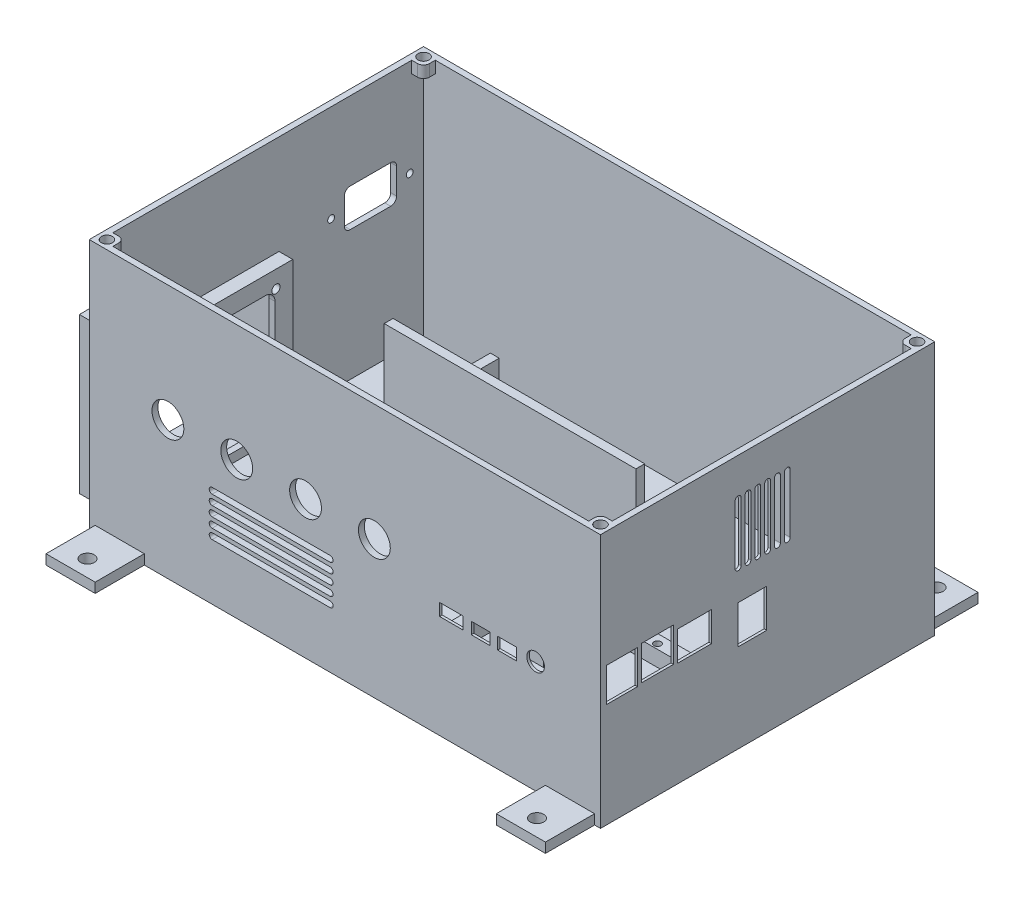
SolidWorks part; units mm, degrees
ref_plane "Front Plane" through (0, 0, 0) normal (0, 0, 1) x (1, 0, 0)
ref_plane "Top Plane" through (0, 0, 0) normal (0, 1, 0) x (1, 0, 0)
ref_plane "Right Plane" through (0, 0, 0) normal (1, 0, 0) x (0, 0, -1)
sketch "Sketch1" plane through (0, 0, 0) normal (0, 1, 0) x (1, 0, 0)
  line L1 (-130, -85) -> (130, -85)
  line L2 (-130, -85) -> (-130, 85)
  line L3 (-130, 85) -> (130, 85)
  line L4 (130, -85) -> (130, 85)
  line L5 (-130, -85) -> (130, 85) construction
  line L6 (-130, 85) -> (130, -85) construction
  point P0 (0, 0)
  dimension "D1" = 170
  dimension "D2" = 260
extrude "Floor" add sketch "Sketch1" along normal blind 4.3805
sketch "Sketch2" plane through (0, 4.3805, 0) normal (0, 1, 0) x (1, 0, 0)
  line L0 (127, -82) -> (127, 82)
  line L1 (127, 82) -> (-127, 82)
  line L2 (-127, 82) -> (-127, -82)
  line L3 (-127, -82) -> (127, -82)
  line L4 (130, -85) -> (130, 85)
  line L5 (130, 85) -> (-130, 85)
  line L6 (-130, 85) -> (-130, -85)
  line L7 (-130, -85) -> (130, -85)
  line L8 (130, -85) -> (130, 85)
  line L9 (130, 85) -> (-130, 85)
  line L10 (-130, 85) -> (-130, -85)
  line L11 (-130, -85) -> (130, -85)
  dimension "D1" = 0
  dimension "D2" = 3
extrude "Wall" add sketch "Sketch2" along normal blind 125
sketch "Sketch4" plane through (0, 4.3805, 0) normal (0, 1, 0) x (1, 0, 0)
  line L0 (120, -33) -> (49, -33)
  line L1 (127, -82) -> (42, -82)
  line L2 (127, -82) -> (127, -26)
  line L3 (127, -26) -> (42, -26)
  line L4 (42, -82) -> (42, -26)
  line L5 (49, -75) -> (49, -33)
  line L6 (120, -75) -> (49, -75)
  line L7 (120, -75) -> (120, -33)
  dimension "D1" = 85
  dimension "D2" = 56
  dimension "D3" = 7
extrude "Rpi stand" add sketch "Sketch4" along normal blind 8 from offset 29
sketch "Sketch7" plane through (0, 129.3805, 0) normal (0, 1, 0) x (1, 0, 0)
sketch "Sketch3" plane through (0, 0, 0) normal (0, 1, 0) x (1, 0, 0)
  line L0 (-114.3, 101.6) -> (114.3, 101.6) construction
  line L1 (-127, 85) -> (-102, 85)
  line L2 (-127, 85) -> (-127, 110)
  line L3 (-127, 110) -> (-102, 110)
  line L4 (-102, 85) -> (-102, 110)
  line L5 (127, 85) -> (102, 85)
  line L6 (127, 85) -> (127, 110)
  line L7 (127, 110) -> (102, 110)
  line L8 (102, 85) -> (102, 110)
  line L9 (-127, -85) -> (-102, -85)
  line L10 (-127, -85) -> (-127, -110)
  line L11 (-127, -110) -> (-102, -110)
  line L12 (-102, -85) -> (-102, -110)
  line L13 (127, -85) -> (102, -85)
  line L14 (127, -85) -> (127, -110)
  line L15 (127, -110) -> (102, -110)
  line L16 (102, -85) -> (102, -110)
  line L17 (114.3, 101.6) -> (114.3, -101.6) construction
  line L18 (114.3, -101.6) -> (-114.3, -101.6) construction
  line L19 (-114.3, -101.6) -> (-114.3, 101.6) construction
  line L20 (-130, 0) -> (130, 0) construction
  line L21 (130, 85) -> (-130, 85) construction
  line L22 (130, -85) -> (130, 85) construction
  line L23 (0, 101.6) -> (0, -101.6) construction
  line L24 (-130, -85) -> (130, -85) construction
  line L26 (-130, 85) -> (-130, -85) construction
  line L27 (-130, -85) -> (130, -85) construction
  circle A0 centre (-114.3, 101.6) radius 3.429
  circle A1 centre (114.3, 101.6) radius 3.429
  circle A2 centre (114.3, -101.6) radius 3.429
  circle A3 centre (-114.3, -101.6) radius 3.429
  point P4 (-130, -85)
  point P9 (130, -85)
  point P28 (-114.5, -85)
  point P29 (-102, -97.5)
  point P30 (114.5, -85)
  point P31 (-102, 97.5)
  dimension "D5" = 6.858
  dimension "D1" = 25
  dimension "D2" = 25
  dimension "D3" = 25
  dimension "D6" = 203.2
  dimension "D7" = 228.6
  dimension "D8" = 3
  dimension "D9" = 3
  dimension "D4" = 25
extrude "Brackets" add sketch "Sketch3" along normal blind 5
sketch "Sketch5" plane through (-130, 0, 0) normal (-1, 0, 0) x (0, 0, 1)
  line L0 (-8.5, 78.8805) -> (70, 78.8805)
  line L1 (-1, 4.3805) -> (62.5, 4.3805)
  line L2 (-4.5, 7.8805) -> (-4.5, 71.3805)
  line L3 (-1, 74.8805) -> (62.5, 74.8805)
  line L4 (66, 7.8805) -> (66, 71.3805)
  line L5 (70, 0.3805) -> (70, 78.8805)
  line L6 (-8.5, 0.3805) -> (70, 0.3805)
  line L7 (-8.5, 0.3805) -> (-8.5, 78.8805)
  line L8 (-4.5, 4.3805) -> (66, 4.3805) construction
  line L9 (110, 5) -> (110, 0) construction
  line L10 (-4.5, 4.3805) -> (-4.5, 74.8805) construction
  line L11 (-82, 4.3805) -> (82, 4.3805) construction
  line L12 (66, 4.3805) -> (66, 74.8805) construction
  line L13 (-4.5, 74.8805) -> (66, 74.8805) construction
  arc A0 (-1, 4.3805) -> (-4.5, 7.8805) centre (-1, 7.8805) cw
  arc A1 (62.5, 4.3805) -> (66, 7.8805) centre (62.5, 7.8805) ccw
  arc A2 (62.5, 74.8805) -> (66, 71.3805) centre (62.5, 71.3805) cw
  arc A3 (-4.5, 71.3805) -> (-1, 74.8805) centre (-1, 71.3805) cw
  dimension "D4" = 3.5
  dimension "D1" = 70.5
  dimension "D2" = 70.5
  dimension "D5" = 40
  dimension "D3" = 4
extrude "Fan Holder" add sketch "Sketch5" along normal blind 20 and the other way blind 10
sketch "Sketch31" plane through (0, 0.3805, 0) normal (0, -1, 0) x (1, 0, 0)
  line L4 (-130, -8.5) -> (-130, 70)
  line L5 (-130, 70) -> (-150, 70)
  line L6 (-150, 70) -> (-150, -8.5)
  line L7 (-150, -8.5) -> (-130, -8.5)
  line L8 (-130, -8.5) -> (-130, 70)
  line L9 (-130, 70) -> (-150, 70)
  line L10 (-150, 70) -> (-150, -8.5)
  line L11 (-150, -8.5) -> (-130, -8.5)
  dimension "D1" = 0
extrude "Bring fan holder to ground" add sketch "Sketch31" along normal up to surface (0.3805 mm away) up to face at (0, 0, 0)
sketch "Sketch8" plane through (-130, 0, 0) normal (-1, 0, 0) x (0, 0, 1)
  line L4 (-4.5, 71.3805) -> (-4.5, 7.8805)
  line L5 (-1, 4.3805) -> (62.5, 4.3805)
  line L6 (66, 7.8805) -> (66, 71.3805)
  line L7 (62.5, 74.8805) -> (-1, 74.8805)
  line L8 (-4.5, 71.3805) -> (-4.5, 7.8805)
  line L9 (-1, 4.3805) -> (62.5, 4.3805)
  line L10 (66, 7.8805) -> (66, 71.3805)
  line L23 (62.5, 74.8805) -> (-1, 74.8805)
  arc A2 (-4.5, 7.8805) -> (-1, 4.3805) centre (-1, 7.8805) ccw
  arc A3 (-4.5, 7.8805) -> (-1, 4.3805) centre (-1, 7.8805) ccw
  arc A4 (62.5, 4.3805) -> (66, 7.8805) centre (62.5, 7.8805) ccw
  arc A5 (62.5, 4.3805) -> (66, 7.8805) centre (62.5, 7.8805) ccw
  arc A8 (66, 71.3805) -> (62.5, 74.8805) centre (62.5, 71.3805) ccw
  arc A14 (66, 71.3805) -> (62.5, 74.8805) centre (62.5, 71.3805) ccw
  arc A16 (-1, 74.8805) -> (-4.5, 71.3805) centre (-1, 71.3805) ccw
  arc A17 (-1, 74.8805) -> (-4.5, 71.3805) centre (-1, 71.3805) ccw
  dimension "D1" = 0
extrude "Fan hole" cut sketch "Sketch8" against normal up to next
sketch "Sketch11" plane through (-120, 0, 0) normal (-1, 0, 0) x (0, 0, 1)
  line L0 (-8.5, 39.4402) -> (70, 39.4402) construction
  line L1 (30.75, 78.8805) -> (30.75, 0.3805) construction
  line L3 (0.05, 8.7402) -> (61.45, 8.7402) construction
  line L4 (-8.5, 78.8805) -> (-8.5, 0)
  line L5 (-8.5, 0) -> (70, 0)
  line L6 (70, 0) -> (70, 78.8805)
  line L7 (70, 78.8805) -> (-8.5, 78.8805)
  line L8 (-8.5, 78.8805) -> (-8.5, 0)
  line L10 (70, 0) -> (70, 78.8805)
  line L11 (70, 78.8805) -> (-8.5, 78.8805)
  line L12 (0.05, 8.7402) -> (0.05, 70.1402) construction
  line L13 (0.05, 70.1402) -> (61.45, 70.1402) construction
  line L14 (61.45, 8.7402) -> (61.45, 70.1402) construction
  line L15 (0.05, 8.7402) -> (61.45, 70.1402) construction
  line L16 (0.5, 69.8805) -> (0.5, 9)
  line L17 (0.5, 9) -> (61, 9)
  line L18 (61, 9) -> (61, 69.8805)
  line L19 (61, 69.8805) -> (0.5, 69.8805)
  line L20 (0.5, 64.8805) -> (0.5, 14)
  line L22 (61, 14) -> (61, 64.8805)
  line L23 (56, 69.8805) -> (5.5, 69.8805)
  line L24 (0.05, 70.1402) -> (61.45, 8.7402) construction
  line L29 (5.5, 9) -> (56, 9)
  line L31 (-8.5, 0) -> (70, 0)
  arc A0 (0.5, 14) -> (5.5, 9) centre (5.5, 14) ccw
  arc A1 (56, 9) -> (61, 14) centre (56, 14) ccw
  arc A2 (61, 64.8805) -> (56, 69.8805) centre (56, 64.8805) ccw
  arc A3 (0.5, 64.8805) -> (5.5, 69.8805) centre (5.5, 64.8805) cw
  circle A4 centre (0.05, 70.1402) radius 2.1
  circle A5 centre (61.45, 70.1402) radius 2.1
  circle A6 centre (61.45, 8.7402) radius 2.1
  circle A7 centre (0.05, 8.7402) radius 2.1
  point P24 (30.75, 39.4402)
  point P34 (30.75, 39.4402)
  dimension "D3" = 5
  dimension "D6" = 4.2
  dimension "D4" = 61.4
  dimension "D5" = 61.4
  dimension "D1" = 0
  dimension "D2" = 9
extrude "Boss-Extrude9" add sketch "Sketch11" along normal blind 3
sketch "Sketch12" plane through (0, 33.3805, 0) normal (0, -1, 0) x (1, 0, 0)
  line L1 (42, 26) -> (49, 26)
  line L2 (42, 26) -> (42, 33)
  line L3 (42, 33) -> (49, 33)
  line L4 (49, 26) -> (49, 33)
  dimension "D1" = 7
  dimension "D2" = 7
extrude "Boss-Extrude10" add sketch "Sketch12" along normal up to next
sketch "Sketch13" plane through (0, 4.3805, 0) normal (0, 1, 0) x (1, 0, 0)
  line L0 (127, 82) -> (-127, 82) construction
  line L2 (-107, -57) -> (-107, 5.7) construction
  line L3 (-107, 5.7) -> (-69.4, 5.7) construction
  line L4 (-107, -57) -> (-69.4, -57) construction
  line L5 (-69.4, 5.7) -> (-69.4, -57) construction
  line L6 (-69.4, 5.7) -> (-57.4, 5.7) construction
  line L7 (-57.4, 5.7) -> (-57.4, -57) construction
  line L8 (-57.4, -57) -> (-19.8, -57) construction
  line L9 (-19.8, -57) -> (-19.8, 5.7) construction
  line L10 (-19.8, 5.7) -> (-57.4, 5.7) construction
  line L11 (-69.4, -57) -> (-57.4, -57) construction
  line L12 (-19.8, -57) -> (62.83, -57) construction
  line L13 (62.83, -57) -> (62.83, -25.4) construction
  line L14 (62.83, -25.4) -> (105, -25.4) construction
  line L15 (105, -25.4) -> (105, -57) construction
  line L16 (105, -57) -> (62.83, -57) construction
  line L17 (118, 82) -> (118, 21.5) construction
  line L18 (-16.3, -57.85) -> (-16.3, 6.55) construction
  line L20 (127, -82) -> (127, 82) construction
  line L21 (118, 21.5) -> (120.7, 21.5) construction
  line L22 (118, 21.5) -> (41.5, 21.5) construction
  line L23 (-6.3, -47) -> (30.69, -47) construction
  line L24 (-6.3, -47) -> (-6.3, -6.4) construction
  line L25 (-6.3, -6.4) -> (30.69, -6.4) construction
  line L26 (30.69, -47) -> (30.69, -6.4) construction
  line L27 (-6.3, -47) -> (30.69, -6.4) construction
  line L28 (-6.3, -6.4) -> (30.69, -47) construction
  line L29 (130, -85) -> (130, 85) construction
  line L30 (-127, -82) -> (127, -82) construction
  line L457 (-127, 8.5) -> (-127, -70) construction
  line L458 (-127, -82) -> (127, -82) construction
  circle A0 centre (-107, -57) radius 1.25
  circle A1 centre (-107, 5.7) radius 1.25
  circle A2 centre (-69.4, 5.7) radius 1.25
  circle A3 centre (-69.4, -57) radius 1.25
  circle A4 centre (-57.4, 5.7) radius 1.25
  circle A5 centre (-57.4, -57) radius 1.25
  circle A6 centre (-19.8, -57) radius 1.25
  circle A7 centre (-19.8, 5.7) radius 1.25
  circle A12 centre (120.7, 21.5) radius 1.25
  circle A13 centre (41.5, 21.5) radius 1.25
  circle A14 centre (-107, 5.7) radius 2.75
  circle A15 centre (-107, -57) radius 2.75
  circle A16 centre (-69.4, 5.7) radius 2.75
  circle A17 centre (-57.4, 5.7) radius 2.75
  circle A18 centre (-69.4, -57) radius 2.75
  circle A19 centre (-57.4, -57) radius 2.75
  circle A20 centre (-19.8, -57) radius 2.75
  circle A21 centre (-19.8, 5.7) radius 2.75
  circle A22 centre (62.83, -57) radius 2.5
  circle A23 centre (62.83, -25.4) radius 2.5
  circle A24 centre (105, -25.4) radius 2.5
  circle A25 centre (105, -57) radius 2.5
  circle A26 centre (-6.3, -47) radius 1.25
  circle A28 centre (-6.3, -47) radius 2.75
  circle A30 centre (-69.4, 5.7) radius 1.65 construction
  circle A31 centre (104.2333, -41.2) radius 1.5 construction
  circle A32 centre (104.2333, -41.2) radius 1.5 construction
  circle A33 centre (63.5933, -41.2) radius 1.5 construction
  circle A34 centre (63.5933, -41.2) radius 1.5 construction
  circle A35 centre (104.2333, -41.2) radius 3
  circle A36 centre (63.5933, -41.2) radius 3
  circle A37 centre (-6.3, -6.4) radius 1.25
  circle A38 centre (30.69, -6.4) radius 1.25
  circle A39 centre (30.69, -47) radius 1.25
  circle A40 centre (-6.3, -6.4) radius 2.75
  circle A41 centre (30.69, -6.4) radius 2.75
  circle A42 centre (30.69, -47) radius 2.75
  circle A43 centre (30.69, -6.4) radius 1.5 construction
  circle A44 centre (30.69, -6.4) radius 1.5 construction
  point P2 (-127, -82)
  point P3 (127, -82)
  point P8 (12.195, -26.7)
  point P31 (127, 82)
  point P32 (-127, 82)
  point P90 (-123, -62.5)
  point P91 (-123, -66)
  point P92 (-130, -70)
  point P93 (-130, 8.5)
  point P94 (-127, 8.5)
  point P95 (-127, -70)
  point P96 (-127, 8.5)
  point P97 (-120, 8.5)
  point P98 (-120, -70)
  point P99 (-127, -70)
  point P100 (-120, 8.5)
  point P101 (-120, -70)
  point P102 (-130, -85)
  point P103 (-127, -85)
  point P104 (-102, -85)
  point P105 (102, -85)
  point P106 (127, -85)
  point P107 (130, -85)
  point P108 (-130, 85)
  point P109 (-130, -85)
  point P110 (130, 85)
  point P111 (127, 85)
  point P112 (102, 85)
  point P113 (-102, 85)
  point P114 (-127, 85)
  point P115 (-130, 85)
  point P116 (130, -85)
  point P117 (130, 85)
  point P118 (-130, 85)
  point P119 (-130, -85)
  point P120 (130, 85)
  point P121 (-130, 85)
  point P122 (130, -85)
  point P123 (130, 85)
  point P124 (-130, -85)
  point P125 (130, -85)
  point P126 (-127, 82)
  point P127 (-127, -82)
  point P128 (127, 82)
  point P129 (-127, 82)
  point P130 (127, -82)
  point P131 (127, 82)
  point P132 (-127, -82)
  point P133 (127, -82)
  point P134 (-127, 82)
  point P135 (-127, 8.5)
  point P136 (-127, -70)
  point P137 (-127, -82)
  point P138 (127, -82)
  point P139 (127, 82)
  point P140 (42, -82)
  point P141 (127, -82)
  point P142 (42, -26)
  point P143 (42, -82)
  point P144 (127, -26)
  point P145 (42, -26)
  point P146 (127, -82)
  point P147 (127, -26)
  point P148 (42, -82)
  point P149 (127, -82)
  point P150 (42, -33)
  point P151 (42, -82)
  point P152 (127, -26)
  point P153 (49, -26)
  point P154 (127, -82)
  point P155 (127, -26)
  point P156 (49, -75)
  point P157 (120, -75)
  point P158 (49, -33)
  point P159 (49, -75)
  point P160 (120, -33)
  point P161 (49, -33)
  point P162 (120, -75)
  point P163 (120, -33)
  point P164 (49, -75)
  point P165 (120, -75)
  point P166 (49, -33)
  point P167 (49, -75)
  point P168 (120, -33)
  point P169 (49, -33)
  point P170 (120, -75)
  point P171 (120, -33)
  point P172 (-102, 110)
  point P173 (-127, 110)
  point P174 (-102, 85)
  point P175 (-102, 110)
  point P176 (-127, 85)
  point P177 (-102, 85)
  point P178 (-127, 110)
  point P179 (-127, 85)
  point P180 (-102, 110)
  point P181 (-127, 110)
  point P182 (-102, 85)
  point P183 (-102, 110)
  point P184 (-127, 110)
  point P185 (-127, 85)
  point P186 (-114.3, 101.6)
  point P187 (-111.0208, 102.6025)
  point P188 (-114.3, 101.6)
  point P189 (-111.0208, 102.6025)
  point P190 (114.3, 101.6)
  point P191 (117.5792, 102.6025)
  point P192 (114.3, 101.6)
  point P193 (117.5792, 102.6025)
  point P194 (127, 85)
  point P195 (127, 110)
  point P196 (127, 110)
  point P197 (102, 110)
  point P198 (102, 110)
  point P199 (102, 85)
  point P200 (127, 85)
  point P201 (127, 110)
  point P202 (127, 110)
  point P203 (102, 110)
  point P204 (102, 110)
  point P205 (102, 85)
  point P206 (102, 85)
  point P207 (127, 85)
  point P208 (-114.3, -101.6)
  point P209 (-111.0208, -100.5975)
  point P210 (-114.3, -101.6)
  point P211 (-111.0208, -100.5975)
  point P212 (-127, -85)
  point P213 (-127, -110)
  point P214 (-127, -110)
  point P215 (-102, -110)
  point P216 (-102, -110)
  point P217 (-102, -85)
  point P218 (-127, -85)
  point P219 (-127, -110)
  point P220 (-127, -110)
  point P221 (-102, -110)
  point P222 (-102, -110)
  point P223 (-102, -85)
  point P224 (-102, -85)
  point P225 (-127, -85)
  point P226 (114.3, -101.6)
  point P227 (117.5792, -100.5975)
  point P228 (114.3, -101.6)
  point P229 (117.5792, -100.5975)
  point P230 (127, -110)
  point P231 (127, -85)
  point P232 (102, -85)
  point P233 (102, -110)
  point P234 (102, -110)
  point P235 (127, -110)
  point P236 (127, -110)
  point P237 (127, -85)
  point P238 (127, -85)
  point P239 (102, -85)
  point P240 (102, -85)
  point P241 (102, -110)
  point P242 (102, -110)
  point P243 (127, -110)
  point P244 (-130, 8.5)
  point P245 (-130, -70)
  point P246 (-120, 8.5)
  point P247 (-127, 8.5)
  point P248 (-130, 8.5)
  point P249 (-150, 8.5)
  point P250 (-120, -70)
  point P251 (-127, -70)
  point P252 (-130, -70)
  point P253 (-150, -70)
  point P254 (-130, -70)
  point P255 (-150, -70)
  point P256 (-130, 8.5)
  point P257 (-150, 8.5)
  point P258 (-120, -70)
  point P259 (-120, 8.5)
  point P260 (-123, 4.5)
  point P261 (-150, 4.5)
  point P262 (-123, 4.5)
  point P263 (-150, 4.5)
  point P264 (-123, 1)
  point P265 (-150, 1)
  point P266 (-123, -62.5)
  point P267 (-150, -62.5)
  point P268 (-123, -66)
  point P269 (-150, -66)
  point P270 (-123, -66)
  point P271 (-150, -66)
  point P272 (-123, -62.5)
  point P273 (-150, -62.5)
  point P274 (-123, 1)
  point P275 (-150, 1)
  point P276 (-150, -70)
  point P277 (-150, 8.5)
  point P278 (-150, 8.5)
  point P279 (-150, -70)
  point P280 (-150, 4.5)
  point P281 (-150, 1)
  point P282 (-150, -62.5)
  point P283 (-150, 1)
  point P284 (-150, -62.5)
  point P285 (-150, -66)
  point P286 (-150, -62.5)
  point P287 (-150, -66)
  point P288 (-150, 1)
  point P289 (-150, -62.5)
  point P290 (-150, 4.5)
  point P291 (-150, 1)
  point P292 (-123, 4.5)
  point P293 (-123, 1)
  point P294 (-123, -62.5)
  point P295 (-123, 1)
  point P296 (-123, 4.5)
  point P297 (-123, 1)
  point P298 (-123, 1)
  point P299 (-123, -62.5)
  point P300 (-123, -62.5)
  point P301 (-123, -66)
  point P302 (-123, -5.5)
  point P303 (-120, -5.5)
  point P304 (-123, -56)
  point P305 (-120, -56)
  point P306 (-123, -61)
  point P307 (-120, -61)
  point P308 (-123, -61)
  point P309 (-120, -61)
  point P310 (-123, -56)
  point P311 (-120, -56)
  point P312 (-123, -5.5)
  point P313 (-120, -5.5)
  point P314 (-123, -0.5)
  point P315 (-120, -0.5)
  point P316 (-123, -0.5)
  point P317 (-120, -0.5)
  point P318 (-123, -0.5)
  point P319 (-123, -5.5)
  point P320 (-123, -56)
  point P321 (-123, -5.5)
  point P322 (-123, -56)
  point P323 (-123, -61)
  point P324 (-123, -56)
  point P325 (-123, -61)
  point P326 (-123, -5.5)
  point P327 (-123, -56)
  point P328 (-123, -0.5)
  point P329 (-123, -5.5)
  point P330 (-120, -5.5)
  point P331 (-120, -0.5)
  point P332 (-120, -56)
  point P333 (-120, -5.5)
  point P334 (-120, -61)
  point P335 (-120, -56)
  point P336 (-120, -61)
  point P337 (-120, -56)
  point P338 (-120, -5.5)
  point P339 (-120, -56)
  point P340 (-120, -5.5)
  point P341 (-120, -0.5)
  point P342 (-123, 2.05)
  point P343 (-123, -2.15)
  point P344 (-120, -2.15)
  point P345 (-120, 2.05)
  point P346 (-123, -59.35)
  point P347 (-123, -63.55)
  point P348 (-120, -63.55)
  point P349 (-120, -59.35)
  point P350 (-123, -59.35)
  point P351 (-123, -63.55)
  point P352 (-120, -63.55)
  point P353 (-120, -59.35)
  point P354 (-123, 2.05)
  point P355 (-123, -2.15)
  point P356 (-120, -2.15)
  point P357 (-120, 2.05)
  point P358 (49, -33)
  point P359 (42, -33)
  point P360 (49, -26)
  point P361 (49, -33)
  point P362 (42, -33)
  point P363 (42, -26)
  point P364 (42, -26)
  point P365 (49, -26)
  point P366 (49, -26)
  point P367 (49, -33)
  point P368 (49, -33)
  point P369 (42, -33)
  point P370 (-130, -85)
  point P371 (130, -85)
  point P372 (-130, -85)
  point P373 (-130, 85)
  point P374 (-130, 85)
  point P375 (130, 85)
  point P376 (130, -85)
  point P377 (130, 85)
  point P378 (-130, -85)
  point P379 (130, 85)
  point P380 (-130, 85)
  point P381 (130, -85)
  point P382 (127, -82)
  point P383 (127, 82)
  point P384 (127, 82)
  point P385 (-127, 82)
  point P386 (-127, 82)
  point P387 (-127, -82)
  point P388 (-127, -82)
  point P389 (127, -82)
  point P390 (130, -85)
  point P391 (130, 85)
  point P392 (130, 85)
  point P393 (-130, 85)
  point P394 (-130, 85)
  point P395 (-130, -85)
  point P396 (-130, -85)
  point P397 (130, -85)
  point P398 (130, -85)
  point P399 (130, 85)
  point P400 (130, 85)
  point P401 (-130, 85)
  point P402 (-130, 85)
  point P403 (-130, -85)
  point P404 (-130, -85)
  point P405 (130, -85)
  point P406 (120, -33)
  point P407 (49, -33)
  point P408 (127, -82)
  point P409 (42, -82)
  point P410 (127, -82)
  point P411 (127, -26)
  point P412 (127, -26)
  point P413 (42, -26)
  point P414 (42, -82)
  point P415 (42, -26)
  point P416 (49, -75)
  point P417 (49, -33)
  point P418 (120, -75)
  point P419 (49, -75)
  point P420 (120, -75)
  point P421 (120, -33)
  point P422 (-114.3, 101.6)
  point P423 (114.3, 101.6)
  point P424 (-127, 85)
  point P425 (-102, 85)
  point P426 (-127, 85)
  point P427 (-127, 110)
  point P428 (-127, 110)
  point P429 (-102, 110)
  point P430 (-102, 85)
  point P431 (-102, 110)
  point P432 (127, 85)
  point P433 (102, 85)
  point P434 (127, 85)
  point P435 (127, 110)
  point P436 (127, 110)
  point P437 (102, 110)
  point P438 (102, 85)
  point P439 (102, 110)
  point P440 (-127, -85)
  point P441 (-102, -85)
  point P442 (-127, -85)
  point P443 (-127, -110)
  point P444 (-127, -110)
  point P445 (-102, -110)
  point P446 (-102, -85)
  point P447 (-102, -110)
  point P448 (127, -85)
  point P449 (102, -85)
  point P450 (127, -85)
  point P451 (127, -110)
  point P452 (127, -110)
  point P453 (102, -110)
  point P454 (102, -85)
  point P455 (102, -110)
  point P456 (114.3, 101.6)
  point P457 (114.3, -101.6)
  point P458 (114.3, -101.6)
  point P459 (-114.3, -101.6)
  point P460 (-114.3, -101.6)
  point P461 (-114.3, 101.6)
  point P462 (-130, 0)
  point P463 (130, 0)
  point P464 (130, 85)
  point P465 (-130, 85)
  point P466 (130, -85)
  point P467 (130, 85)
  point P468 (0, 101.6)
  point P469 (0, -101.6)
  point P470 (-130, 85)
  point P471 (-130, -85)
  point P472 (-130, -85)
  point P473 (130, -85)
  point P474 (-130, 8.5)
  point P475 (-130, -70)
  point P476 (-130, 1)
  point P477 (-130, -62.5)
  point P478 (-130, 1)
  point P479 (-130, -62.5)
  point P480 (-130, 8.5)
  point P481 (-130, -70)
  point P482 (-130, 4.5)
  point P483 (-130, -66)
  point P484 (-130, 82)
  point P485 (-130, -82)
  point P486 (-130, 4.5)
  point P487 (-130, -66)
  point P488 (-130, 1)
  point P489 (-130, -62.5)
  point P490 (-130, -62.5)
  point P491 (-130, 1)
  point P492 (-130, 1)
  point P493 (-130, -62.5)
  point P494 (-130, -62.5)
  point P495 (-130, 1)
  point P496 (-120, 8.5)
  point P497 (-120, -70)
  point P498 (-120, -0.05)
  point P499 (-120, -61.45)
  point P500 (-120, 8.5)
  point P501 (-120, -70)
  point P502 (-120, -70)
  point P503 (-120, 8.5)
  point P504 (-120, 8.5)
  point P505 (-120, -70)
  point P506 (-120, -70)
  point P507 (-120, 8.5)
  point P508 (-120, -0.05)
  point P509 (-120, -61.45)
  point P510 (-120, -0.05)
  point P511 (-120, -61.45)
  point P512 (-120, -0.5)
  point P513 (-120, -61)
  point P514 (-120, -61)
  point P515 (-120, -0.5)
  point P516 (-120, -5.5)
  point P517 (-120, -56)
  point P518 (-120, -56)
  point P519 (-120, -5.5)
  point P520 (-120, -0.05)
  point P521 (-120, -61.45)
  point P522 (42, -26)
  point P523 (49, -26)
  point P524 (42, -26)
  point P525 (42, -33)
  point P526 (42, -33)
  point P527 (49, -33)
  point P528 (49, -26)
  point P529 (49, -33)
  point P530 (-123, -62.5)
  point P531 (-123, -66)
  point P532 (-130, -70)
  point P533 (-130, 8.5)
  point P534 (-127, 8.5)
  point P535 (-127, -70)
  point P536 (-127, 8.5)
  point P537 (-120, 8.5)
  point P538 (-120, -70)
  point P539 (-127, -70)
  point P540 (-120, 8.5)
  point P541 (-120, -70)
  point P542 (-130, -85)
  point P543 (-127, -85)
  point P544 (-102, -85)
  point P545 (102, -85)
  point P546 (127, -85)
  point P547 (130, -85)
  point P548 (-130, 85)
  point P549 (-130, -85)
  point P550 (130, 85)
  point P551 (127, 85)
  point P552 (102, 85)
  point P553 (-102, 85)
  point P554 (-127, 85)
  point P555 (-130, 85)
  point P556 (130, -85)
  point P557 (130, 85)
  point P558 (-130, 85)
  point P559 (-130, -85)
  point P560 (130, 85)
  point P561 (-130, 85)
  point P562 (130, -85)
  point P563 (130, 85)
  point P564 (-130, -85)
  point P565 (130, -85)
  point P566 (-127, 82)
  point P567 (-127, -82)
  point P568 (127, 82)
  point P569 (-127, 82)
  point P570 (127, -82)
  point P571 (127, 82)
  point P572 (-127, -82)
  point P573 (127, -82)
  point P574 (-127, 82)
  point P575 (-127, 8.5)
  point P576 (-127, -70)
  point P577 (-127, -82)
  point P578 (127, 82)
  point P579 (-127, 82)
  point P580 (127, -82)
  point P581 (127, 82)
  point P582 (-127, -82)
  point P583 (127, -82)
  point P584 (42, -82)
  point P585 (127, -82)
  point P586 (42, -26)
  point P587 (42, -82)
  point P588 (127, -26)
  point P589 (42, -26)
  point P590 (127, -82)
  point P591 (127, -26)
  point P592 (42, -82)
  point P593 (127, -82)
  point P594 (42, -33)
  point P595 (42, -82)
  point P596 (127, -26)
  point P597 (49, -26)
  point P598 (127, -82)
  point P599 (127, -26)
  point P600 (49, -75)
  point P601 (120, -75)
  point P602 (49, -33)
  point P603 (49, -75)
  point P604 (120, -33)
  point P605 (49, -33)
  point P606 (120, -75)
  point P607 (120, -33)
  point P608 (49, -75)
  point P609 (120, -75)
  point P610 (49, -33)
  point P611 (49, -75)
  point P612 (120, -33)
  point P613 (49, -33)
  point P614 (120, -75)
  point P615 (120, -33)
  point P616 (-102, 110)
  point P617 (-127, 110)
  point P618 (-102, 85)
  point P619 (-102, 110)
  point P620 (-127, 85)
  point P621 (-102, 85)
  point P622 (-127, 110)
  point P623 (-127, 85)
  point P624 (-102, 110)
  point P625 (-127, 110)
  point P626 (-102, 85)
  point P627 (-102, 110)
  point P628 (-127, 110)
  point P629 (-127, 85)
  point P630 (-114.3, 101.6)
  point P631 (-111.0208, 102.6025)
  point P632 (-114.3, 101.6)
  point P633 (-111.0208, 102.6025)
  point P634 (114.3, 101.6)
  point P635 (117.5792, 102.6025)
  point P636 (114.3, 101.6)
  point P637 (117.5792, 102.6025)
  point P638 (127, 85)
  point P639 (127, 110)
  point P640 (127, 110)
  point P641 (102, 110)
  point P642 (102, 110)
  point P643 (102, 85)
  point P644 (127, 85)
  point P645 (127, 110)
  point P646 (127, 110)
  point P647 (102, 110)
  point P648 (102, 110)
  point P649 (102, 85)
  point P650 (102, 85)
  point P651 (127, 85)
  point P652 (-114.3, -101.6)
  point P653 (-111.0208, -100.5975)
  point P654 (-114.3, -101.6)
  point P655 (-111.0208, -100.5975)
  point P656 (-127, -85)
  point P657 (-127, -110)
  point P658 (-127, -110)
  point P659 (-102, -110)
  point P660 (-102, -110)
  point P661 (-102, -85)
  point P662 (-127, -85)
  point P663 (-127, -110)
  point P664 (-127, -110)
  point P665 (-102, -110)
  point P666 (-102, -110)
  point P667 (-102, -85)
  point P668 (-102, -85)
  point P669 (-127, -85)
  point P670 (114.3, -101.6)
  point P671 (117.5792, -100.5975)
  point P672 (114.3, -101.6)
  point P673 (117.5792, -100.5975)
  point P674 (127, -110)
  point P675 (127, -85)
  point P676 (102, -85)
  point P677 (102, -110)
  point P678 (102, -110)
  point P679 (127, -110)
  point P680 (127, -110)
  point P681 (127, -85)
  point P682 (127, -85)
  point P683 (102, -85)
  point P684 (102, -85)
  point P685 (102, -110)
  point P686 (102, -110)
  point P687 (127, -110)
  point P688 (-130, 8.5)
  point P689 (-130, -70)
  point P690 (-120, 8.5)
  point P691 (-127, 8.5)
  point P692 (-130, 8.5)
  point P693 (-150, 8.5)
  point P694 (-120, -70)
  point P695 (-127, -70)
  point P696 (-130, -70)
  point P697 (-150, -70)
  point P698 (-130, -70)
  point P699 (-150, -70)
  point P700 (-130, 8.5)
  point P701 (-150, 8.5)
  point P702 (-120, -70)
  point P703 (-120, 8.5)
  point P704 (-123, 4.5)
  point P705 (-150, 4.5)
  point P706 (-123, 4.5)
  point P707 (-150, 4.5)
  point P708 (-123, 1)
  point P709 (-150, 1)
  point P710 (-123, -62.5)
  point P711 (-150, -62.5)
  point P712 (-123, -66)
  point P713 (-150, -66)
  point P714 (-123, -66)
  point P715 (-150, -66)
  point P716 (-123, -62.5)
  point P717 (-150, -62.5)
  point P718 (-123, 1)
  point P719 (-150, 1)
  point P720 (-150, -70)
  point P721 (-150, 8.5)
  point P722 (-150, 8.5)
  point P723 (-150, -70)
  point P724 (-150, 4.5)
  point P725 (-150, 1)
  point P726 (-150, -62.5)
  point P727 (-150, 1)
  point P728 (-150, -62.5)
  point P729 (-150, -66)
  point P730 (-150, -62.5)
  point P731 (-150, -66)
  point P732 (-150, 1)
  point P733 (-150, -62.5)
  point P734 (-150, 4.5)
  point P735 (-150, 1)
  point P736 (-123, 4.5)
  point P737 (-123, 1)
  point P738 (-123, -62.5)
  point P739 (-123, 1)
  point P740 (-123, 4.5)
  point P741 (-123, 1)
  point P742 (-123, 1)
  point P743 (-123, -62.5)
  point P744 (-123, -62.5)
  point P745 (-123, -66)
  point P746 (-123, -5.5)
  point P747 (-120, -5.5)
  point P748 (-123, -56)
  point P749 (-120, -56)
  point P750 (-123, -61)
  point P751 (-120, -61)
  point P752 (-123, -61)
  point P753 (-120, -61)
  point P754 (-123, -56)
  point P755 (-120, -56)
  point P756 (-123, -5.5)
  point P757 (-120, -5.5)
  point P758 (-123, -0.5)
  point P759 (-120, -0.5)
  point P760 (-123, -0.5)
  point P761 (-120, -0.5)
  point P762 (-123, -0.5)
  point P763 (-123, -5.5)
  point P764 (-123, -56)
  point P765 (-123, -5.5)
  point P766 (-123, -56)
  point P767 (-123, -61)
  point P768 (-123, -56)
  point P769 (-123, -61)
  point P770 (-123, -5.5)
  point P771 (-123, -56)
  point P772 (-123, -0.5)
  point P773 (-123, -5.5)
  point P774 (-120, -5.5)
  point P775 (-120, -0.5)
  point P776 (-120, -56)
  point P777 (-120, -5.5)
  point P778 (-120, -61)
  point P779 (-120, -56)
  point P780 (-120, -61)
  point P781 (-120, -56)
  point P782 (-120, -5.5)
  point P783 (-120, -56)
  point P784 (-120, -5.5)
  point P785 (-120, -0.5)
  point P786 (-123, 2.05)
  point P787 (-123, -2.15)
  point P788 (-120, -2.15)
  point P789 (-120, 2.05)
  point P790 (-123, -59.35)
  point P791 (-123, -63.55)
  point P792 (-120, -63.55)
  point P793 (-120, -59.35)
  point P794 (-123, -59.35)
  point P795 (-123, -63.55)
  point P796 (-120, -63.55)
  point P797 (-120, -59.35)
  point P798 (-123, 2.05)
  point P799 (-123, -2.15)
  point P800 (-120, -2.15)
  point P801 (-120, 2.05)
  point P802 (49, -33)
  point P803 (42, -33)
  point P804 (49, -26)
  point P805 (49, -33)
  point P806 (42, -33)
  point P807 (42, -26)
  point P808 (42, -26)
  point P809 (49, -26)
  point P810 (49, -26)
  point P811 (49, -33)
  point P812 (49, -33)
  point P813 (42, -33)
  point P814 (-130, -85)
  point P815 (130, -85)
  point P816 (-130, -85)
  point P817 (-130, 85)
  point P818 (-130, 85)
  point P819 (130, 85)
  point P820 (130, -85)
  point P821 (130, 85)
  point P822 (-130, -85)
  point P823 (130, 85)
  point P824 (-130, 85)
  point P825 (130, -85)
  point P826 (127, -82)
  point P827 (127, 82)
  point P828 (127, 82)
  point P829 (-127, 82)
  point P830 (-127, 82)
  point P831 (-127, -82)
  point P832 (-127, -82)
  point P833 (127, -82)
  point P834 (130, -85)
  point P835 (130, 85)
  point P836 (130, 85)
  point P837 (-130, 85)
  point P838 (-130, 85)
  point P839 (-130, -85)
  point P840 (-130, -85)
  point P841 (130, -85)
  point P842 (130, -85)
  point P843 (130, 85)
  point P844 (130, 85)
  point P845 (-130, 85)
  point P846 (-130, 85)
  point P847 (-130, -85)
  point P848 (-130, -85)
  point P849 (130, -85)
  point P850 (120, -33)
  point P851 (49, -33)
  point P852 (127, -82)
  point P853 (42, -82)
  point P854 (127, -82)
  point P855 (127, -26)
  point P856 (127, -26)
  point P857 (42, -26)
  point P858 (42, -82)
  point P859 (42, -26)
  point P860 (49, -75)
  point P861 (49, -33)
  point P862 (120, -75)
  point P863 (49, -75)
  point P864 (120, -75)
  point P865 (120, -33)
  point P866 (-114.3, 101.6)
  point P867 (114.3, 101.6)
  point P868 (-127, 85)
  point P869 (-102, 85)
  point P870 (-127, 85)
  point P871 (-127, 110)
  point P872 (-127, 110)
  point P873 (-102, 110)
  point P874 (-102, 85)
  point P875 (-102, 110)
  point P876 (127, 85)
  point P877 (102, 85)
  point P878 (127, 85)
  point P879 (127, 110)
  point P880 (127, 110)
  point P881 (102, 110)
  point P882 (102, 85)
  point P883 (102, 110)
  point P884 (-127, -85)
  point P885 (-102, -85)
  point P886 (-127, -85)
  point P887 (-127, -110)
  point P888 (-127, -110)
  point P889 (-102, -110)
  point P890 (-102, -85)
  point P891 (-102, -110)
  point P892 (127, -85)
  point P893 (102, -85)
  point P894 (127, -85)
  point P895 (127, -110)
  point P896 (127, -110)
  point P897 (102, -110)
  point P898 (102, -85)
  point P899 (102, -110)
  point P900 (114.3, 101.6)
  point P901 (114.3, -101.6)
  point P902 (114.3, -101.6)
  point P903 (-114.3, -101.6)
  point P904 (-114.3, -101.6)
  point P905 (-114.3, 101.6)
  point P906 (-130, 0)
  point P907 (130, 0)
  point P908 (130, 85)
  point P909 (-130, 85)
  point P910 (130, -85)
  point P911 (130, 85)
  point P912 (0, 101.6)
  point P913 (0, -101.6)
  point P914 (-130, 85)
  point P915 (-130, -85)
  point P916 (-130, -85)
  point P917 (130, -85)
  point P918 (-130, 8.5)
  point P919 (-130, -70)
  point P920 (-130, 1)
  point P921 (-130, -62.5)
  point P922 (-130, 1)
  point P923 (-130, -62.5)
  point P924 (-130, 8.5)
  point P925 (-130, -70)
  point P926 (-130, 4.5)
  point P927 (-130, -66)
  point P928 (-130, 82)
  point P929 (-130, -82)
  point P930 (-130, 4.5)
  point P931 (-130, -66)
  point P932 (-130, 1)
  point P933 (-130, -62.5)
  point P934 (-130, -62.5)
  point P935 (-130, 1)
  point P936 (-130, 1)
  point P937 (-130, -62.5)
  point P938 (-130, -62.5)
  point P939 (-130, 1)
  point P940 (-120, 8.5)
  point P941 (-120, -70)
  point P942 (-120, -0.05)
  point P943 (-120, -61.45)
  point P944 (-120, 8.5)
  point P945 (-120, -70)
  point P946 (-120, -70)
  point P947 (-120, 8.5)
  point P948 (-120, 8.5)
  point P949 (-120, -70)
  point P950 (-120, -70)
  point P951 (-120, 8.5)
  point P952 (-120, -0.05)
  point P953 (-120, -61.45)
  point P954 (-120, -0.05)
  point P955 (-120, -61.45)
  point P956 (-120, -0.5)
  point P957 (-120, -61)
  point P958 (-120, -61)
  point P959 (-120, -0.5)
  point P960 (-120, -5.5)
  point P961 (-120, -56)
  point P962 (-120, -56)
  point P963 (-120, -5.5)
  point P964 (-120, -0.05)
  point P965 (-120, -61.45)
  point P966 (42, -26)
  point P967 (49, -26)
  point P968 (42, -26)
  point P969 (42, -33)
  point P970 (42, -33)
  point P971 (49, -33)
  point P972 (49, -26)
  point P973 (49, -33)
  dimension "D3" = 2.5
  dimension "D6" = 1.5
  dimension "D7" = 2.5
  dimension "D8" = 10
  dimension "D11" = 35
  dimension "D12" = 20
  dimension "D13" = 25
  dimension "D25" = 2.5
  dimension "D27" = 2.5
  dimension "D4" = 5
  dimension "D5" = 25
  dimension "D9" = 12
  dimension "D10" = 1.5
  dimension "D17" = 31.6
  dimension "D19" = 42.17
  dimension "D22" = 60.5
  dimension "D23" = 9
  dimension "D24" = 2.7
  dimension "D26" = 76.5
  dimension "D28" = 1.5
extrude "Built in Standoffs" add sketch "Sketch13" along normal blind 5 contours A1 | A16 A2 | A2 | A17 A4 | A4 | A14 A1 | A21 A7 | A7 | A15 A0 | A0 | A18 A3 | A3 | A19 A5 | A5 | A20 A6 | A6 | A22 | A23 | A24 A32 | A32 | A25 | A36 | A35 | A28 A26 | A26 | A40 A37 | A37 | A41 A38 | A38 | A42 A39 | A39 region at (-107, 4.3805, 57) region at (-107, 4.3805, -5.7) region at (-69.4, 4.3805, -5.7) region at (-69.4, 4.3805, 57) region at (-57.4, 4.3805, -5.7) region at (-57.4, 4.3805, 57) region at (-19.8, 4.3805, 57) region at (-19.8, 4.3805, -5.7) region at (-109.6722, 4.3805, -5.7) region at (-109.6722, 4.3805, 57) region at (-72.0722, 4.3805, -5.7) region at (-60.0722, 4.3805, -5.7) region at (-72.0722, 4.3805, 57) region at (-60.0722, 4.3805, 57) region at (-22.4722, 4.3805, 57) region at (-22.4722, 4.3805, -5.7) region at (62.83, 4.3805, 57) region at (62.83, 4.3805, 25.4) region at (105, 4.3805, 25.4) region at (105, 4.3805, 57) region at (-6.3, 4.3805, 47) region at (-8.9722, 4.3805, 47) region at (104.2333, 4.3805, 41.2) region at (63.5933, 4.3805, 41.2) region at (-6.3, 4.3805, 6.4) region at (30.69, 4.3805, 6.4) region at (30.69, 4.3805, 47) region at (-8.9722, 4.3805, 6.4) region at (28.0178, 4.3805, 6.4) region at (28.0178, 4.3805, 47)
sketch "Sketch19" plane through (0, 9.3805, 0) normal (0, 1, 0) x (1, 0, 0)
  circle A0 centre (104.2333, -41.2) radius 1.25
  circle A1 centre (63.5933, -41.2) radius 1.25
  dimension "D1" = 2.5
  dimension "D2" = 2.5
extrude "Bread board holes" cut sketch "Sketch19" against normal blind 7
sketch "Sketch14" plane through (0, 4.3805, 0) normal (0, 1, 0) x (1, 0, 0)
  line L0 (127, 82) -> (-88, 82)
  line L1 (127, 82) -> (-127, 82) construction
  line L2 (-88, 82) -> (-88, 32)
  line L3 (-88, 32) -> (127, 32)
  line L4 (127, -82) -> (127, 82) construction
  line L5 (127, 32) -> (127, 82)
  dimension "D1" = 215
  dimension "D2" = 50
extrude "Screw Holes" cut sketch "Sketch13<4>" against normal blind 7 from surface contours A37 | A38 | A26 | A39 | A1 | A0 | A3 | A5 | A2 | A4 | A7 | A6 | A32 region at (-6.3, 4.3805, 47) region at (-6.3, 4.3805, 6.4) region at (30.69, 4.3805, 6.4) region at (30.69, 4.3805, 47) starting at face at (-107, 9.3805, -2.95)
sketch "Sketch13<4>" plane through (0, 4.3805, 0) normal (0, 1, 0) x (1, 0, 0) same geometry as "Sketch13"
extrude "Driver Screw Holes" cut sketch "Sketch13<5>" against normal blind 3 contours A13 | A12
sketch "Sketch13<5>" plane through (0, 4.3805, 0) normal (0, 1, 0) x (1, 0, 0) same geometry as "Sketch13"
sketch "Sketch16" plane through (0, 4.3805, 0) normal (0, 1, 0) x (1, 0, 0)
  line L0 (-93, 82) -> (-93, 28)
  line L1 (-93, 28) -> (35, 28)
  line L2 (-88.5, 82) -> (-88.5, 32.5)
  line L3 (-88.5, 32.5) -> (35, 32.5)
  line L10 (-88, 82) -> (-88, 33) construction
  line L11 (-88, 33) -> (29.1074, 33) construction
  line L14 (-93, 28) -> (127, 28) construction
  line L16 (-88, 33) -> (127, 33) construction
  line L17 (-88.5, 82) -> (-93, 82)
  line L20 (35, 28) -> (35, 32.5)
  line L21 (-88.5, 32.5) -> (29.1074, 32.5) construction
  line L25 (-88, 33) -> (127, 33)
  line L26 (127, 33) -> (127, 82)
  line L27 (127, 82) -> (-88, 82)
  line L28 (-88, 82) -> (-88, 33)
  line L29 (-88, 33) -> (127, 33) construction
  line L30 (127, 33) -> (127, 82) construction
  line L31 (127, 82) -> (-88, 82) construction
  line L32 (-88, 82) -> (-88, 33) construction
  line L57 (-88, 82) -> (-88, 33) construction
  line L58 (127, 82) -> (-127, 82) construction
  dimension "D3" = 0.5
  dimension "D5" = 128
  dimension "D1" = 0
  dimension "D2" = 5
extrude "Power supply wall" add sketch "Sketch16" along normal blind 10 contours L2 L3 L20 L1 L0 L17
sketch "Sketch25" plane through (0, 14.3805, 0) normal (0, 1, 0) x (1, 0, 0)
  line L0 (-93, 82) -> (-93, 28) construction
  line L1 (35, 28) -> (-93, 28)
  line L2 (35, 28) -> (35, 32.5)
  line L3 (35, 32.5) -> (-93, 32.5)
  line L4 (-93, 28) -> (-93, 32.5)
  line L5 (-88.5, 32.5) -> (35, 32.5) construction
  line L6 (-88.5, 32.5) -> (35, 32.5) construction
extrude "Boss-Extrude11" add sketch "Sketch25" along normal blind 40
sketch "Sketch17" plane through (0, 41.3805, 0) normal (0, 1, 0) x (1, 0, 0)
  circle A0 centre (46.5, -30.5) radius 1.7859
  circle A1 centre (104.5, -30.5) radius 1.7859
  circle A2 centre (104.5, -79.5) radius 1.7859
  circle A3 centre (46.5, -79.5) radius 1.7859
  dimension "D1" = 3.5719
extrude "rpi standoff holes" cut sketch "Sketch17" against normal blind 6
sketch "Sketch20" plane through (0, 0, 85) normal (0, 0, 1) x (1, 0, 0)
  line L1 (49.6827, 57.1504) -> (58.6882, 57.1504) construction
  line L2 (49.6827, 57.1504) -> (49.6827, 53.9554) construction
  line L3 (49.6827, 53.9554) -> (58.6882, 53.9554) construction
  line L4 (58.6882, 57.1504) -> (58.6882, 53.9554) construction
  line L5 (79.2167, 56.9908) -> (85.8798, 56.9908) construction
  line L6 (79.2167, 56.9908) -> (79.2167, 53.9258) construction
  line L7 (79.2167, 53.9258) -> (85.8798, 53.9258) construction
  line L8 (85.8798, 56.9908) -> (85.8798, 53.9258) construction
  line L9 (65.7798, 56.9112) -> (72.2962, 56.9112) construction
  line L10 (65.7798, 56.9112) -> (65.7798, 53.9475) construction
  line L11 (65.7798, 53.9475) -> (72.2962, 53.9475) construction
  line L12 (72.2962, 56.9112) -> (72.2962, 53.9475) construction
  line L13 (48.1827, 58.6504) -> (60.1882, 58.6504)
  line L14 (60.1882, 58.6504) -> (60.1882, 52.4554)
  line L15 (48.1827, 52.4554) -> (60.1882, 52.4554)
  line L16 (48.1827, 58.6504) -> (48.1827, 52.4554)
  line L17 (77.7167, 58.4908) -> (87.3798, 58.4908)
  line L18 (87.3798, 58.4908) -> (87.3798, 52.4258)
  line L19 (77.7167, 52.4258) -> (87.3798, 52.4258)
  line L20 (77.7167, 58.4908) -> (77.7167, 52.4258)
  line L21 (64.2798, 58.4112) -> (73.7962, 58.4112)
  line L22 (73.7962, 58.4112) -> (73.7962, 52.4475)
  line L23 (64.2798, 52.4475) -> (73.7962, 52.4475)
  line L24 (64.2798, 58.4112) -> (64.2798, 52.4475)
  circle A0 centre (97, 56.9705) radius 4.5
  dimension "D1" = 9
  dimension "D2" = 1.5
extrude "Cut-Extrude5" cut sketch "Sketch20" against normal up to next
sketch "Sketch21" plane through (0, 129.3805, 0) normal (0, 1, 0) x (1, 0, 0)
  line L0 (125, -26.3) -> (46, -26.3) construction
  line L1 (42.3, -30) -> (42.3, -80) construction
  line L2 (46, -83.7) -> (125, -83.7)
  line L3 (128.7, -80) -> (128.7, -30)
  line L4 (128, -80) -> (128, -30)
  line L5 (125, -27) -> (46, -27)
  line L6 (43, -30) -> (43, -80)
  line L7 (46, -83) -> (125, -83)
  line L8 (128, -80) -> (128, -30) construction
  line L9 (125, -27) -> (46, -27) construction
  line L10 (43, -30) -> (43, -80) construction
  line L11 (46, -83) -> (125, -83) construction
  line L28 (46, -83.7) -> (20.659, -83.7)
  line L29 (20.659, -83.7) -> (20.659, 4.3626)
  line L30 (20.659, 4.3626) -> (128.7, 4.3626)
  line L31 (128.7, 4.3626) -> (128.7, -30)
  arc A0 (46, -26.3) -> (42.3, -30) centre (46, -30) ccw construction
  arc A1 (42.3, -80) -> (46, -83.7) centre (46, -80) ccw construction
  arc A2 (125, -83.7) -> (128.7, -80) centre (125, -80) ccw
  arc A3 (128.7, -30) -> (125, -26.3) centre (125, -30) ccw construction
  arc A4 (128, -30) -> (125, -27) centre (125, -30) ccw
  arc A5 (46, -27) -> (43, -30) centre (46, -30) ccw
  arc A6 (43, -80) -> (46, -83) centre (46, -80) ccw
  arc A7 (125, -83) -> (128, -80) centre (125, -80) ccw
  arc A8 (128, -30) -> (125, -27) centre (125, -30) ccw construction
  arc A9 (46, -27) -> (43, -30) centre (46, -30) ccw construction
  arc A10 (43, -80) -> (46, -83) centre (46, -80) ccw construction
  arc A11 (125, -83) -> (128, -80) centre (125, -80) ccw construction
  dimension "D1" = 0
  dimension "D2" = 0.7
extrude "Rpi Room" cut sketch "Sketch21" against normal up to surface (88 mm away) from offset 20 contours L2 A2 L3 L31 L30 L29 L28 up to face at (46.5, 41.3805, 81.2859) offset against normal yes
sketch "Sketch22" plane through (130, 0, 0) normal (1, 0, 0) x (0, 0, -1)
  line L0 (-81.966, 70.2905) -> (-66.1499, 70.2905)
  line L1 (-81.166, 69.4905) -> (-66.9499, 69.4905) construction
  line L2 (-81.166, 69.4905) -> (-81.166, 53.8427) construction
  line L3 (-81.166, 53.8427) -> (-66.9499, 53.8427) construction
  line L4 (-66.9499, 69.4905) -> (-66.9499, 53.8427) construction
  line L5 (-63.3011, 70.2905) -> (-48.6526, 70.2905) construction
  line L6 (-63.3011, 70.2905) -> (-63.3011, 54.5222) construction
  line L7 (-63.3011, 54.5222) -> (-48.6526, 54.5222) construction
  line L8 (-48.6526, 70.2905) -> (-48.6526, 54.5222) construction
  line L9 (-45.1414, 67.4119) -> (-29.3586, 67.4119) construction
  line L10 (-45.1414, 67.4119) -> (-45.1414, 53.9605) construction
  line L11 (-45.1414, 53.9605) -> (-29.3586, 53.9605) construction
  line L12 (-29.3586, 67.4119) -> (-29.3586, 53.9605) construction
  line L13 (-66.1499, 70.2905) -> (-66.1499, 53.0427)
  line L14 (-81.966, 53.0427) -> (-66.1499, 53.0427)
  line L15 (-81.966, 70.2905) -> (-81.966, 53.0427)
  line L16 (-64.1011, 71.0905) -> (-47.8526, 71.0905)
  line L17 (-47.8526, 71.0905) -> (-47.8526, 53.7222)
  line L18 (-64.1011, 53.7222) -> (-47.8526, 53.7222)
  line L19 (-64.1011, 71.0905) -> (-64.1011, 53.7222)
  line L20 (-45.9414, 68.2119) -> (-28.5586, 68.2119)
  line L21 (-28.5586, 68.2119) -> (-28.5586, 53.1605)
  line L22 (-45.9414, 53.1605) -> (-28.5586, 53.1605)
  line L23 (-45.9414, 68.2119) -> (-45.9414, 53.1605)
  line L24 (-70.9672, 69.4905) -> (-73.95, 69.4905) construction
  line L25 (-85, 129.3805) -> (-85, 0) construction
  line L26 (-85, 0) -> (85, 0) construction
  arc A0 (-29.3, 67.2705) -> (-29.5, 67.4705) centre (-29.5, 67.2705) ccw construction
  dimension "D2" = 3.834
  dimension "D3" = 14.2161
  dimension "D4" = 15.6478
  dimension "D5" = 3.6488
  dimension "D6" = 14.6485
  dimension "D7" = 15.7683
  dimension "D8" = 70.2905
  dimension "D9" = 13.4514
  dimension "D1" = 0.8
extrude "Cut-Extrude7" cut sketch "Sketch22" against normal up to next
sketch "Sketch24" plane through (0, 0, -85) normal (0, 0, -1) x (-1, 0, 0)
  circle A0 centre (-83.6, 40.8805) radius 30 construction
  circle A1 centre (-83.6, 40.8805) radius 30 construction
  circle A2 centre (-83.6, 40.8805) radius 32
  dimension "D1" = 2
extrude "Cut-Extrude8" cut sketch "Sketch24" against normal up to next
sketch "Sketch26" plane through (130, 0, 0) normal (1, 0, 0) x (0, 0, -1)
  line L0 (-15, 80) -> (-15, 110) construction
  line L1 (-16.5, 80) -> (-16.5, 110)
  line L2 (-13.5, 80) -> (-13.5, 110)
  line L3 (-85, 0) -> (85, 0) construction
  line L4 (-85, 129.3805) -> (-85, 0) construction
  line L5 (-10, 80) -> (-10, 110) construction
  line L6 (-11.5, 80) -> (-11.5, 110)
  line L7 (-8.5, 80) -> (-8.5, 110)
  line L8 (-5, 80) -> (-5, 110) construction
  line L9 (-6.5, 80) -> (-6.5, 110)
  line L10 (-3.5, 80) -> (-3.5, 110)
  line L11 (0, 80) -> (0, 110) construction
  line L12 (-1.5, 80) -> (-1.5, 110)
  line L13 (1.5, 80) -> (1.5, 110)
  line L14 (5, 80) -> (5, 110) construction
  line L15 (3.5, 80) -> (3.5, 110)
  line L16 (6.5, 80) -> (6.5, 110)
  line L17 (10, 80) -> (10, 110) construction
  line L18 (8.5, 80) -> (8.5, 110)
  line L19 (11.5, 80) -> (11.5, 110)
  arc A0 (-16.5, 80) -> (-13.5, 80) centre (-15, 80) ccw
  arc A1 (-13.5, 110) -> (-16.5, 110) centre (-15, 110) ccw
  arc A2 (-11.5, 80) -> (-8.5, 80) centre (-10, 80) ccw
  arc A3 (-8.5, 110) -> (-11.5, 110) centre (-10, 110) ccw
  arc A4 (-6.5, 80) -> (-3.5, 80) centre (-5, 80) ccw
  arc A5 (-3.5, 110) -> (-6.5, 110) centre (-5, 110) ccw
  arc A6 (-1.5, 80) -> (1.5, 80) centre (0, 80) ccw
  arc A7 (1.5, 110) -> (-1.5, 110) centre (0, 110) ccw
  arc A8 (3.5, 80) -> (6.5, 80) centre (5, 80) ccw
  arc A9 (6.5, 110) -> (3.5, 110) centre (5, 110) ccw
  arc A10 (8.5, 80) -> (11.5, 80) centre (10, 80) ccw
  arc A11 (11.5, 110) -> (8.5, 110) centre (10, 110) ccw
  point P2 (-15, 95)
  point P14 (-10, 95)
  point P21 (-5, 95)
  point P28 (0, 95)
  point P35 (5, 95)
  point P42 (10, 95)
  dimension "D1" = 30
  dimension "D2" = 3
  dimension "D3" = 80
  dimension "D4" = 70
  dimension "D6" = 5
  dimension "D5" = 6
extrude "vent 1" cut sketch "Sketch26" against normal up to next
sketch "Sketch27" plane through (0, 129.3805, 0) normal (0, 1, 0) x (1, 0, 0)
  line L0 (0, 0) -> (0, 85) construction
  line L1 (130, 85) -> (121, 85)
  line L2 (130, 85) -> (130, 76)
  line L3 (130, 76) -> (124, 76)
  line L4 (121, 85) -> (121, 79)
  line L18 (-130, 0) -> (130, 0) construction
  line L20 (-121, 85) -> (-121, 79)
  line L21 (-130, 76) -> (-124, 76)
  line L22 (-130, 85) -> (-130, 76)
  line L23 (-130, 85) -> (-121, 85)
  line L24 (-130, -85) -> (-121, -85)
  line L25 (-130, -85) -> (-130, -76)
  line L26 (-130, -76) -> (-124, -76)
  line L27 (-121, -85) -> (-121, -79)
  line L28 (121, -85) -> (121, -79)
  line L29 (130, -76) -> (124, -76)
  line L30 (130, -85) -> (130, -76)
  line L31 (130, -85) -> (121, -85)
  circle A0 centre (125.5, 80.5) radius 2.8067
  circle A1 centre (-125.5, 80.5) radius 2.8067
  circle A2 centre (-125.5, -80.5) radius 2.8067
  circle A3 centre (125.5, -80.5) radius 2.8067
  arc A4 (124, 76) -> (121, 79) centre (124, 79) cw
  arc A5 (121, -79) -> (124, -76) centre (124, -79) cw
  arc A6 (-124, -76) -> (-121, -79) centre (-124, -79) cw
  arc A7 (-121, 79) -> (-124, 76) centre (-124, 79) cw
  point P23 (121, 76)
  point P35 (121, -76)
  point P38 (-121, -76)
  point P41 (-121, 76)
  dimension "D1" = 5.6134
  dimension "D5" = 3
  dimension "D6" = 3
  dimension "D2" = 4.5
  dimension "D3" = 4.5
  dimension "D4" = 9
extrude "Boss-Extrude12" add sketch "Sketch27" against normal blind 6 contours L21 A7 L20 L23 L22 | L30 L29 A5 L28 L31 | L2 L3 A4 L4 L1 | L24 L27 A6 L26 L25
extrude "lid holes" cut sketch "Sketch27<3>" against normal blind 4.8 contours A0 | A1 | A2 | A3
sketch "Sketch27<3>" plane through (0, 129.3805, 0) normal (0, 1, 0) x (1, 0, 0) same geometry as "Sketch27"
sketch "Sketch28" plane through (0, 0, 85) normal (0, 0, 1) x (1, 0, 0)
  line L0 (-102, 0) -> (102, 0) construction
  line L1 (-130, 129.3805) -> (-130, 0) construction
  line L2 (-90, 70) -> (-55, 70) construction
  circle A0 centre (-90, 70) radius 8.1
  circle A4 centre (-55, 70) radius 8.1
  circle A5 centre (-20, 70) radius 8.1
  circle A6 centre (15, 70) radius 8.1
  dimension "D1" = 16.2
  dimension "D2" = 70
  dimension "D3" = 40
  dimension "D5" = 35
  dimension "D4" = 4
extrude "Connectors hole" cut sketch "Sketch28" against normal up to next
sketch "Sketch32" plane through (130, 0, 0) normal (1, 0, 0) x (0, 0, -1)
  line L0 (-85, 0) -> (85, 0) construction
  line L1 (-15, 64.45) -> (-0.45, 64.45)
  line L2 (-15, 64.45) -> (-15, 45)
  line L3 (-15, 45) -> (-0.45, 45)
  line L4 (-0.45, 64.45) -> (-0.45, 45)
  line L5 (-85, 129.3805) -> (-85, 0) construction
  dimension "D1" = 19.45
  dimension "D2" = 14.55
  dimension "D3" = 45
  dimension "D4" = 70
extrude "Ethernet" cut sketch "Sketch32" against normal up to next contours L1 L4 L3 L2
sketch "Sketch33" plane through (-130, 0, 0) normal (-1, 0, 0) x (0, 0, 1)
  line L0 (-75, 80) -> (-35, 80) construction
  line L1 (-65.3, 70.4) -> (-44.7, 70.4)
  line L2 (-68.3, 73.4) -> (-68.3, 86.6)
  line L3 (-65.3, 89.6) -> (-44.7, 89.6)
  line L4 (-41.7, 73.4) -> (-41.7, 86.6)
  line L5 (-55, 89.6) -> (-55, 70.4) construction
  line L6 (-85, 129.3805) -> (-85, 0) construction
  line L7 (-85, 0) -> (-8.5, 0) construction
  circle A0 centre (-75, 80) radius 1.75
  circle A1 centre (-35, 80) radius 1.75
  arc A2 (-65.3, 70.4) -> (-68.3, 73.4) centre (-65.3, 73.4) cw
  arc A3 (-44.7, 70.4) -> (-41.7, 73.4) centre (-44.7, 73.4) ccw
  arc A4 (-44.7, 89.6) -> (-41.7, 86.6) centre (-44.7, 86.6) cw
  arc A5 (-68.3, 86.6) -> (-65.3, 89.6) centre (-65.3, 86.6) cw
  point P8 (-55, 80)
  point P15 (-41.7, 70.4)
  point P18 (-41.7, 89.6)
  point P21 (-68.3, 89.6)
  dimension "D4" = 3.5
  dimension "D5" = 3.5
  dimension "D6" = 3
  dimension "D1" = 26.6
  dimension "D2" = 19.2
  dimension "D3" = 40
  dimension "D7" = 30
  dimension "D8" = 80
extrude "power supply socket" cut sketch "Sketch33" against normal up to next
sketch "Sketch34" plane through (0, 0, 85) normal (0, 0, 1) x (1, 0, 0)
  line L0 (-67.5, 50) -> (-7.5, 50) construction
  line L1 (-67.5, 51.5) -> (-7.5, 51.5)
  line L2 (-67.5, 48.5) -> (-7.5, 48.5)
  line L3 (-102, 0) -> (102, 0) construction
  line L4 (-55, 70) -> (-20, 70) construction
  line L5 (-67.5, 45) -> (-7.5, 45) construction
  line L6 (-67.5, 46.5) -> (-7.5, 46.5)
  line L7 (-67.5, 43.5) -> (-7.5, 43.5)
  line L8 (-67.5, 40) -> (-7.5, 40) construction
  line L9 (-67.5, 41.5) -> (-7.5, 41.5)
  line L10 (-67.5, 38.5) -> (-7.5, 38.5)
  line L11 (-67.5, 35) -> (-7.5, 35) construction
  line L12 (-67.5, 36.5) -> (-7.5, 36.5)
  line L13 (-67.5, 33.5) -> (-7.5, 33.5)
  line L14 (-67.5, 30) -> (-7.5, 30) construction
  line L15 (-67.5, 31.5) -> (-7.5, 31.5)
  line L16 (-67.5, 28.5) -> (-7.5, 28.5)
  arc A0 (-67.5, 51.5) -> (-67.5, 48.5) centre (-67.5, 50) ccw
  arc A1 (-7.5, 48.5) -> (-7.5, 51.5) centre (-7.5, 50) ccw
  circle A2 centre (-20, 70) radius 8.1 construction
  circle A3 centre (-55, 70) radius 8.1 construction
  circle A4 centre (-20, 70) radius 8.1 construction
  circle A5 centre (-55, 70) radius 8.1 construction
  arc A6 (-67.5, 46.5) -> (-67.5, 43.5) centre (-67.5, 45) ccw
  arc A7 (-7.5, 43.5) -> (-7.5, 46.5) centre (-7.5, 45) ccw
  arc A8 (-67.5, 41.5) -> (-67.5, 38.5) centre (-67.5, 40) ccw
  arc A9 (-7.5, 38.5) -> (-7.5, 41.5) centre (-7.5, 40) ccw
  arc A10 (-67.5, 36.5) -> (-67.5, 33.5) centre (-67.5, 35) ccw
  arc A11 (-7.5, 33.5) -> (-7.5, 36.5) centre (-7.5, 35) ccw
  arc A12 (-67.5, 31.5) -> (-67.5, 28.5) centre (-67.5, 30) ccw
  arc A13 (-7.5, 28.5) -> (-7.5, 31.5) centre (-7.5, 30) ccw
  point P2 (-37.5, 50)
  point P15 (-37.5, 70)
  point P19 (-37.5, 45)
  point P26 (-37.5, 40)
  point P33 (-37.5, 35)
  point P40 (-37.5, 30)
  dimension "D1" = 50
  dimension "D2" = 3
  dimension "D3" = 60
  dimension "D5" = 5
  dimension "D4" = 5
extrude "vent 2" cut sketch "Sketch34" against normal up to next
sketch "Sketch35" plane through (0, 0, 0) normal (0, 0, 1) x (1, 0, 0)
  line L0 (127, 123.3805) -> (127, 4.3805) construction
  line L1 (127, 123.3805) -> (127, 4.3805) construction
  line L2 (127, 25) -> (119.5, 25)
  line L3 (119.5, 40) -> (123, 40)
  line L4 (127, 28) -> (119.5, 28)
  line L5 (119.5, 37) -> (123, 37)
  line L6 (123, 40) -> (123, 37)
  line L7 (127, 28) -> (127, 25)
  line L8 (123, 40) -> (123, 37)
  line L10 (102, 0) -> (127, 0) construction
  arc A0 (119.5, 25) -> (119.5, 40) centre (119.5, 32.5) cw
  arc A1 (119.5, 28) -> (119.5, 37) centre (119.5, 32.5) cw
  point P12 (112, 32.5)
  dimension "D3" = 15
  dimension "D1" = 4
  dimension "D4" = 25
  dimension "D5" = 15
  dimension "D2" = 3
extrude "Boss-Extrude15" add sketch "Sketch35" along normal blind 3 from offset 10 contours L4 A1 L5 L6 L3 A0 L2 L7 region at (123.25, 25.2121, 0)
equation "\"D2@Sketch3\"=\"D1@Sketch3\""
equation "\"D3@Sketch27\"=\"D4@Sketch27\"/2"
equation "\"D2@Sketch27\"=\"D3@Sketch27\""
